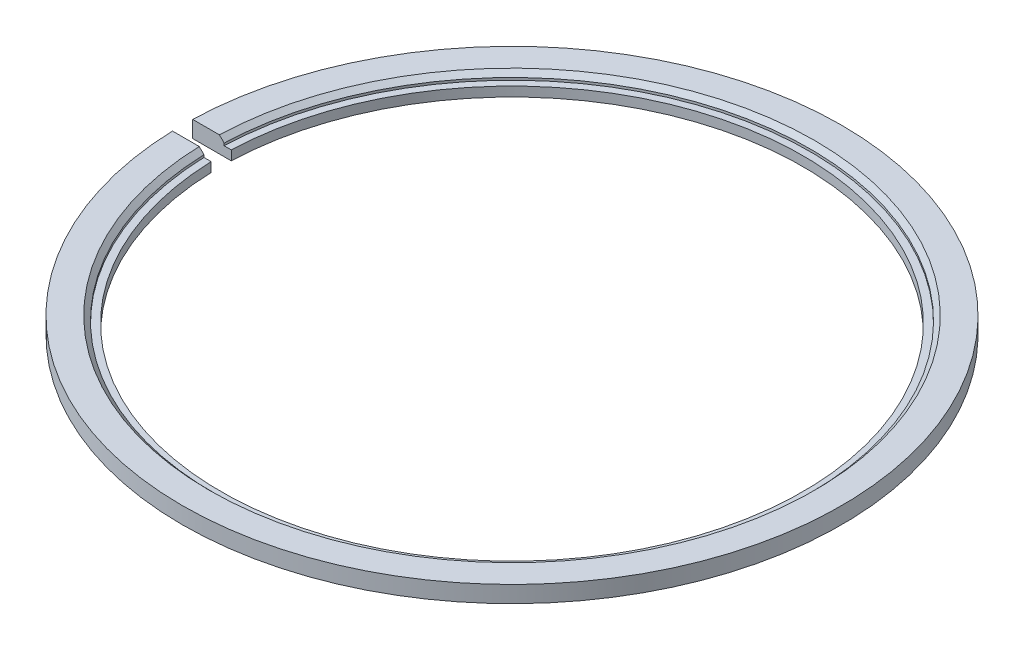
SolidWorks part; units mm, degrees
material "AISI 1045 Steel, cold drawn"
ref_plane "Front Plane" through (0, 0, 0) normal (0, 0, 1) x (1, 0, 0)
ref_plane "Top Plane" through (0, 0, 0) normal (0, 1, 0) x (1, 0, 0)
ref_plane "Right Plane" through (0, 0, 0) normal (1, 0, 0) x (0, 0, -1)
sketch "Primary Sketch" plane through (0, 0, 0) normal (0, 0, 1) x (1, 0, 0)
  line L0 (4.1275, 1.778) -> (4.1275, 0)
  line L1 (0, 0) -> (4.1275, 0) construction
  line L2 (0, 0) -> (0, 1.778) construction
  line L3 (0, 1.778) -> (4.1275, 1.778) construction
  line L4 (4.1275, 0) -> (4.1275, 1.778) construction
  line L5 (4.1275, 0) -> (0, 0)
  line L6 (0, 0) -> (0, 1.016)
  line L9 (0, 1.016) -> (0.762, 1.016)
  line L10 (0.762, 1.016) -> (0.762, 1.778)
  line L11 (0.762, 1.778) -> (4.1275, 1.778)
  line L12 (0, 0) -> (-31.115, 0) construction
  line L13 (-31.115, 0) -> (-31.115, 5.265) construction
  dimension "D1" = 1.016
  dimension "D2" = 0.762
  dimension "D3" = 1.778
  dimension "D4" = 62.23
  dimension "D5" = 70.485
revolve "Primary Revolve" add sketch "Primary Sketch" angle 360 about L13
chamfer "Inner Chamfer" distance 0.508 angle 45 1 edges at (0.762, 1.778, 0)
sketch "Slit Sketch" plane through (0, 0, 0) normal (0, 0, 1) x (1, 0, 0)
  line L0 (4.1275, 1.778) -> (-66.3575, 1.778) construction
  line L1 (-74.9711, 3.3924) -> (-49.522, 3.3924)
  line L2 (-74.9711, 3.3924) -> (-74.9711, 0)
  line L3 (-74.9711, 0) -> (-49.522, 0)
  line L4 (-49.522, 3.3924) -> (-49.522, 0)
  line L7 (-66.3575, 0) -> (4.1275, 0) construction
  point P4 (-66.8097, 0)
  point P5 (0, 0)
  point P6 (0, 0)
  point P7 (0, 0)
  point P8 (0, 0)
  point P10 (0, 0)
  point P14 (0, 0)
  point P15 (0, 0)
  point P16 (0, 0)
  point P17 (0, 0)
  dimension "D1" = 3.3924
  dimension "D2" = 25.4491
  dimension "D3" = 8.1614
  dimension "D4" = 49.522
extrude "Slit Cut" cut sketch "Slit Sketch" against normal blind 1.0795 and the other way blind 1.0795
